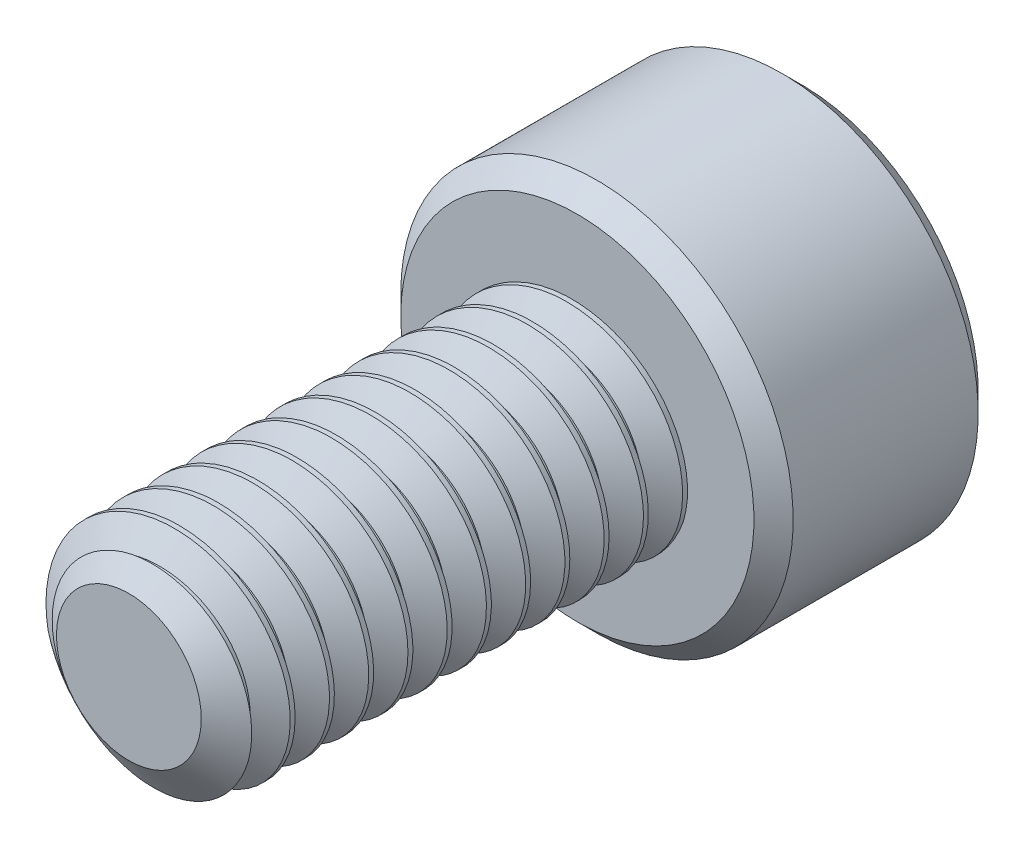
SolidWorks part; units mm, degrees
ref_plane "Front Plane" through (0, 0, 0) normal (0, 0, 1) x (1, 0, 0)
ref_plane "Top Plane" through (0, 0, 0) normal (0, 1, 0) x (1, 0, 0)
ref_plane "Right Plane" through (0, 0, 0) normal (1, 0, 0) x (0, 0, -1)
sketch "Sketch1" plane through (0, 0, 0) normal (0, 0, 1) x (1, 0, 0)
  circle A0 centre (0, 0) radius 2
  dimension "OD" = 4
extrude "Extrude1" add sketch "Sketch1" against normal blind 8
sketch "Sketch2" plane through (0, 0, 0) normal (0, 0, 1) x (1, 0, 0)
  circle A0 centre (0, 0) radius 2 construction
  circle A1 centre (0, 0) radius 2
curve "Helix/Spiral1" pitch 0.7 height 8.7 radius 2 centre (0, 0, 0) axis (0, 0, -1) start towards (0, 1, 0) parameters "pitch"=0.7
sketch "Sketch3" plane through (0, 0, 0) normal (1, 0, 0) x (0, 0, -1)
  line L0 (-0.6125, 2) -> (-0.35, 1.5453)
  line L1 (-0.35, 1.5453) -> (-0.2625, 1.5453)
  line L2 (-0.2625, 1.5453) -> (0, 2)
  line L3 (-0.6125, 2) -> (0, 2)
  line L4 (-0.3062, 2) -> (-0.3062, 1.5453) construction
  line L5 (-0.4812, 1.7727) -> (-0.1312, 1.7727) construction
  line L6 (0, 2) -> (0, -2) construction
  dimension "D1" = 0.0875
  dimension "D2" = 0.35
  dimension "D3" = 60
sweep "Cut-Sweep1" cut profiles "Sketch3" path "Helix/Spiral1" align with end faces yes
sketch "Sketch4" plane through (0, 0, 0) normal (1, 0, 0) x (0, 0, -1)
  line L0 (0.4962, 2) -> (0, 1.2913)
  line L1 (0, 1.2913) -> (0, 2)
  line L2 (0.4962, 2) -> (0, 2)
  line L3 (-0.6125, 2) -> (0, 2) construction
  line L4 (0, 0) -> (7.0209, 0) construction
  dimension "D1" = 55
  dimension "D2" = 0.254
revolve "Cut-Revolve1" cut sketch "Sketch4" angle 360 about L4
sketch "Sketch5" plane through (0, 0, 0) normal (1, 0, 0) x (0, 0, -1)
  line L0 (8, -0.6429) -> (8, 1.6418) construction
  line L1 (8, 2.127) -> (1.2679, 2.127)
  line L2 (8, 2.127) -> (8, 0)
  line L3 (8, 0) -> (1, 0)
  line L4 (1, 1.127) -> (1, 0)
  line L5 (1.2679, 2.127) -> (1, 1.127)
  line L6 (0, 0) -> (1, 0) construction
  point P3 (1, 2.127)
  point P10 (1, 2.127)
  dimension "D1" = 1
  dimension "D2" = 0.127
  dimension "D3" = 15
  dimension "Thread Min" = 1
revolve "partially thread" [suppressed] add sketch "Sketch5" angle 360 about L6
sketch "Sketch6" plane through (0, 0, -8) normal (0, 0, -1) x (-1, 0, 0)
  circle A0 centre (0, 0) radius 3.5
  dimension "head dia" = 7
extrude "Extrude2" add sketch "Sketch6" along normal blind 4
sketch "Sketch7" plane through (0, 0, -12) normal (0, 0, -1) x (-1, 0, 0)
  line L1 (0, 1.7321) -> (-1.5, 0.866)
  line L2 (-1.5, 0.866) -> (-1.5, -0.866)
  line L3 (-1.5, -0.866) -> (0, -1.7321)
  line L4 (0, -1.7321) -> (1.5, -0.866)
  line L5 (1.5, -0.866) -> (1.5, 0.866)
  line L6 (1.5, 0.866) -> (0, 1.7321)
  circle A0 centre (0, 0) radius 1.5 construction
  dimension "hex dia" = 3
extrude "Cut-Extrude1" cut sketch "Sketch7" against normal blind 2.25
sketch "Sketch8" plane through (0, 0, -12) normal (0, 0, -1) x (-1, 0, 0)
  circle A0 centre (0, 0) radius 1.7321
extrude "Cut-Extrude2" cut sketch "Sketch8" against normal through all draft 45
chamfer "Chamfer1" distance 0.35 angle 45 2 edges at (-3.5, 0, -12) (-3.5, 0, -8)
sketch "Sketch9" plane through (0, 0, 0) normal (1, 0, 0) x (0, 0, -1)
  line L0 (0, 2) -> (0, -2) construction
  line L1 (3.85, 2) -> (3.85, -2) construction
  dimension "D1" = 3.85
equation "\"D3@Helix/Spiral1\" = \"screw length@Extrude1\"+\"pitch@Helix/Spiral1\""
equation "\"D1@Sketch3\" = \"pitch@Helix/Spiral1\"*.125"
equation "\"D2@Sketch3\" = \"pitch@Helix/Spiral1\"*.5"
equation "\"D1@Cut-Extrude1\" = \"hex dia@Sketch7\"*.75"
equation "\"D1@Chamfer1\" = \"head dia@Sketch6\"*.05"
equation "\"D1@Sketch9\" = \"pitch@Helix/Spiral1\"*5.5"
